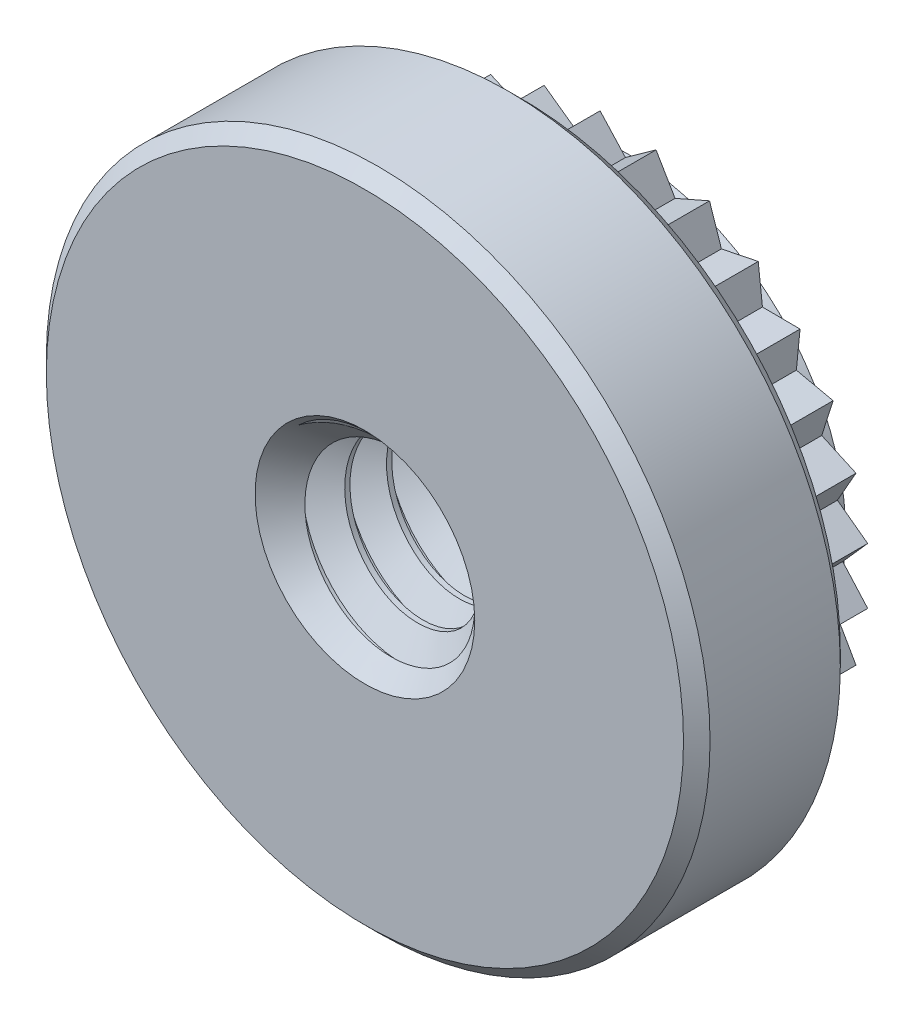
SolidWorks part; units mm, degrees
ref_plane "Front Plane" through (0, 0, 0) normal (0, 0, 1) x (1, 0, 0)
ref_plane "Top Plane" through (0, 0, 0) normal (0, 1, 0) x (1, 0, 0)
ref_plane "Right Plane" through (0, 0, 0) normal (1, 0, 0) x (0, 0, -1)
sketch "Sketch1" plane through (0, 0, 0) normal (0, 0, 1) x (1, 0, 0)
  circle A0 centre (0, 0) radius 3.175
  dimension "A" = 6.35
extrude "Extrude1" add sketch "Sketch1" against normal blind 1.5
sketch "Sketch15" plane through (0, 0, -1.5) normal (0, 0, -1) x (-1, 0, 0)
  circle A0 centre (0, 0) radius 2.1
  dimension "hole dia" = 4.2
sketch "Sketch2" plane through (0, 0, -1.5) normal (0, 0, -1) x (-1, 0, 0)
  circle A0 centre (0, 0) radius 2.1125
  dimension "D1" = 4.225
extrude "Extrude2" add sketch "Sketch2" along normal blind 1
sketch "Sketch3" plane through (0, 0, -2.5) normal (0, 0, -1) x (-1, 0, 0)
  line L0 (0, 1.922) -> (0, 3.175)
  circle A1 centre (0, 0) radius 3.175 construction
  circle A2 centre (0, 0) radius 1.922
  circle A3 centre (0, 0) radius 1.922 construction
  dimension "D1" = 0.1905
sketch "Sketch5" plane through (0, 0, -2.5) normal (0, 0, -1) x (-1, 0, 0)
  circle A0 centre (0, 0) radius 3.175 construction
  circle A3 centre (0, 0) radius 2.1
  dimension "C" = 4.2
extrude "Cut-Extrude1" cut sketch "Sketch5" against normal blind 0.25 draft 20 flip side to cut draft outward yes
chamfer "Chamfer2" distance 0.127 angle 45 2 edges at (3.175, 0, 0) (3.175, 0, -1.5)
sketch "Sketch7" plane through (0, 0, 0) normal (0, 0, 1) x (1, 0, 0)
  circle A0 centre (0, 0) radius 1
  dimension "Thread Od" = 2
extrude "Cut-Extrude3" cut sketch "Sketch7" against normal through all
sketch "Sketch8" plane through (0, 0, -2.5) normal (0, 0, -1) x (-1, 0, 0)
  circle A0 centre (0, 0) radius 1 construction
  circle A1 centre (0, 0) radius 1
curve "Helix/Spiral1" pitch 0.4 height 4.5 radius 1 centre (0, 0, -2.5) axis (0, 0, 1) start towards (0, 1, 0) parameters "pitch"=0.4
sketch "Sketch9" plane through (0, 0, 0) normal (1, 0, 0) x (0, 0, -1)
  line L0 (2.85, 1) -> (2.7, 0.7402)
  line L1 (2.7, 0.7402) -> (2.65, 0.7402)
  line L2 (2.65, 0.7402) -> (2.5, 1)
  line L3 (2.85, 1) -> (2.5, 1)
  line L4 (2.675, 1) -> (2.675, 0.7402) construction
  line L5 (2.775, 0.8701) -> (2.575, 0.8701) construction
  line L6 (2.5, -1) -> (2.5, 1) construction
  dimension "D1" = 60
  dimension "D2" = 0.05
  dimension "D3" = 0.2
sweep "Sweep1" add profiles "Sketch9" path "Helix/Spiral1"
sketch "Sketch10" plane through (0, 0, 0) normal (0, 0, 1) x (1, 0, 0)
  circle A0 centre (0, 0) radius 3.175 construction
  circle A1 centre (0, 0) radius 3.175
extrude "Cut-Extrude4" cut sketch "Sketch10" along normal through all
sketch "Sketch11" plane through (0, 0, -2.5) normal (0, 0, -1) x (-1, 0, 0)
  circle A1 centre (0, 0) radius 2.1 construction
  circle A2 centre (0, 0) radius 2.1
extrude "Cut-Extrude5" cut sketch "Sketch11" along normal through all
sketch "Sketch13" plane through (0, 0, 0) normal (0, 0, 1) x (1, 0, 0)
  circle A2 centre (0, 0) radius 1.0508
  circle A3 centre (0, 0) radius 1.0508
  dimension "D1" = 0.0508
extrude "Cut-Extrude6" cut sketch "Sketch13" against normal through all draft 45
sketch "Sketch14" plane through (0, 0, -2.5) normal (0, 0, -1) x (-1, 0, 0)
  circle A2 centre (0, 0) radius 1.0635
  circle A3 centre (0, 0) radius 1.0635
  dimension "D1" = 0.0635
extrude "Cut-Extrude7" cut sketch "Sketch14" against normal through all draft 45
sketch "Sketch16" plane through (0, 0, -2.25) normal (0, 0, -1) x (-1, 0, 0)
  line L0 (0, 2.1) -> (0, 3.048) construction
  line L1 (0, 2.574) -> (-0.4694, 2.0597)
  line L2 (0, 2.574) -> (0.4694, 2.0597)
  circle A0 centre (0, 0) radius 2.009 construction
  circle A1 centre (0, 0) radius 2.1 construction
  circle A2 centre (0, 0) radius 3.048 construction
  circle A3 centre (0, 0) radius 2.1125 construction
  arc A4 (-0.4694, 2.0597) -> (0.4694, 2.0597) centre (0, 0) cw
  circle A5 centre (0, 0) radius 2.1125 construction
  point P2 (0, 2.574)
  dimension "D2" = 0.9389
extrude "Boss-Extrude1" add sketch "Sketch16" against normal up to surface (0.75 mm away) up to face at (3.048, 0, -1.5)
pattern_circular "CirPattern4" count 30 over 360 about axis through (0, 0, -2.5) along (0, 0, -1) of "Boss-Extrude1"
equation "\"D3@Helix/Spiral1\"=\"B@Extrude1\"+\"panel min.@Extrude2\"+2"
equation "\"D2@Sketch9\" = \"pitch@Helix/Spiral1\"*.125"
equation "\"D3@Sketch9\" = \"pitch@Helix/Spiral1\"*.50"
equation "\"D1@Sketch2\" = \"hole dia@Sketch15\"+.025"
equation "\"D1@Cut-Extrude1\" = \"panel min.@Extrude2\"*.25"
equation "\"D2@Sketch16\"=\"D1@Sketch2\"/4.5"
equation "\"D1@CirPattern4\"=360/12"
